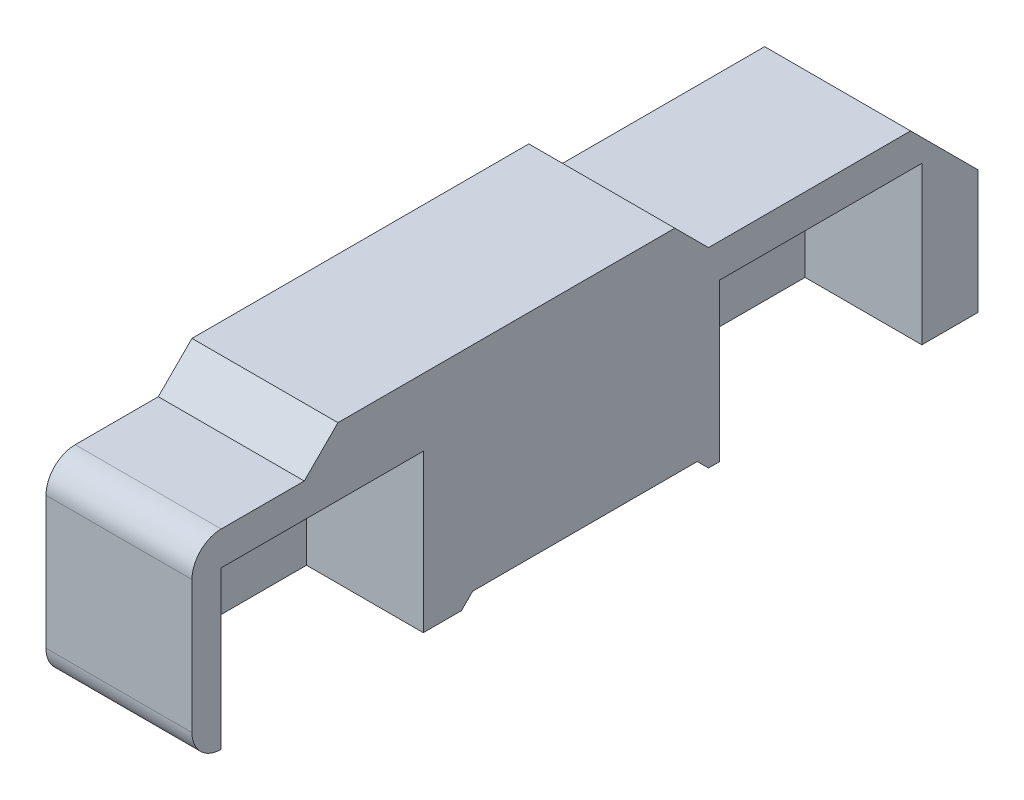
SolidWorks part; units mm, degrees
ref_plane "Front Plane" through (0, 0, 0) normal (0, 0, 1) x (1, 0, 0)
ref_plane "Top Plane" through (0, 0, 0) normal (0, 1, 0) x (1, 0, 0)
ref_plane "Right Plane" through (0, 0, 0) normal (1, 0, 0) x (0, 0, -1)
sketch "Sketch1" plane through (0, 0, 0) normal (0, 1, 0) x (1, 0, 0)
  line L1 (0, 0) -> (150, 0)
  line L2 (0, 0) -> (0, 350)
  line L3 (0, 350) -> (150, 350)
  line L4 (150, 0) -> (150, 350)
  dimension "D1" = 150
  dimension "D2" = 350
sketch "Sketch2" plane through (0, 0, 0) normal (1, 0, 0) x (0, 0, -1)
  line L0 (0, 0) -> (350, 0) construction
  line L1 (0, 0) -> (0, 85)
  line L2 (0, 85) -> (50, 85)
  line L3 (50, 85) -> (65, 100)
  line L4 (65, 100) -> (215, 100)
  line L5 (215, 100) -> (230, 85)
  line L6 (230, 85) -> (320, 85)
  line L7 (320, 85) -> (350, 55)
  line L8 (350, 55) -> (350, 0)
  line L9 (0, 0) -> (120, 0)
  line L10 (120, 0) -> (125, 5)
  line L11 (125, 5) -> (225, 5)
  line L12 (225, 5) -> (230, 0)
  line L13 (230, 0) -> (350, 0)
  dimension "D1" = 350
  dimension "D2" = 85
  dimension "D3" = 50
  dimension "D4" = 15
  dimension "D5" = 150
  dimension "D6" = 90
  dimension "D7" = 135
  dimension "D8" = 120
  dimension "D9" = 5
  dimension "D10" = 45
extrude "Boss-Extrude1" add sketch "Sketch2" along normal blind 65
fillet "Fillet1" radius 13 2 edges at (32.5, 0, 0) (32.5, 85, 0)
sketch "Sketch3" plane through (65, 0, 0) normal (1, 0, 0) x (0, 0, -1)
  line L0 (230, 0) -> (350, 0) construction
  line L1 (13, 0) -> (103, 0)
  line L2 (13, 0) -> (13, 70)
  line L3 (13, 70) -> (103, 70)
  line L4 (103, 0) -> (103, 70)
  line L5 (235, 70) -> (325, 70)
  line L6 (235, 70) -> (235, 0)
  line L7 (235, 0) -> (325, 0)
  line L8 (325, 70) -> (325, 0)
  dimension "D1" = 90
  dimension "D2" = 70
  dimension "D3" = 90
  dimension "D4" = 70
  dimension "D5" = 5
extrude "Cut-Extrude1" cut sketch "Sketch3" against normal blind 52
